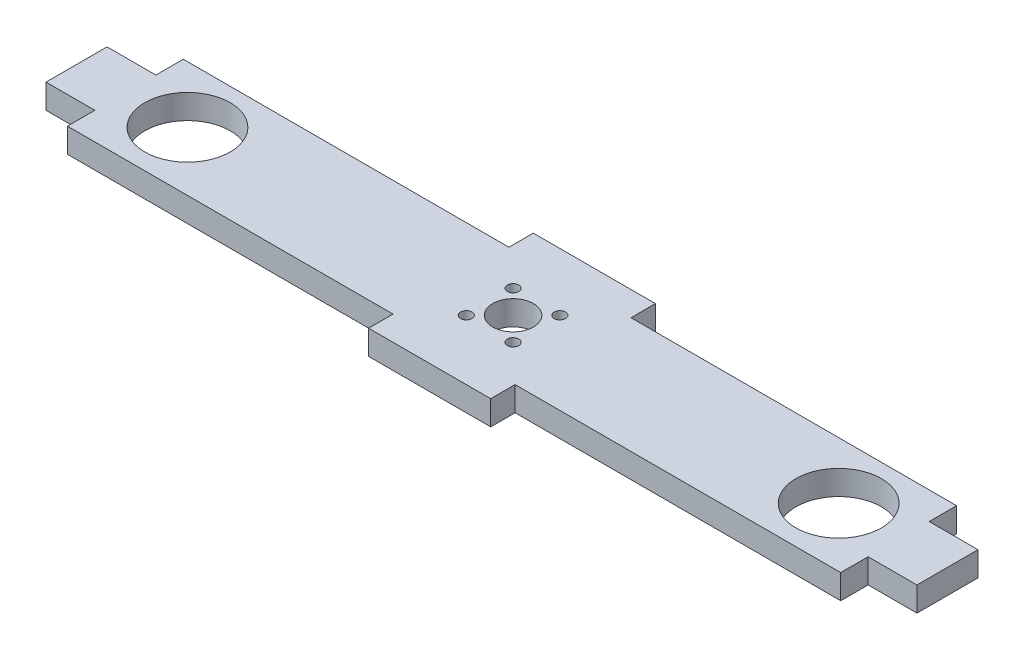
SolidWorks part; units mm, degrees
ref_plane "Front" through (0, 0, 0) normal (0, 0, 1) x (1, 0, 0)
ref_plane "Top" through (0, 0, 0) normal (0, 1, 0) x (1, 0, 0)
ref_plane "Right" through (0, 0, 0) normal (1, 0, 0) x (0, 0, -1)
sketch "Эскиз1" plane through (0, 0, 0) normal (0, 1, 0) x (1, 0, 0)
  line L0 (110.5788, 0.265) -> (-105.6913, 0.265) construction
  line L1 (-95, 14.235) -> (-15, 14.235)
  line L2 (-95, 14.235) -> (-95, 7.5)
  line L3 (-95, -14.235) -> (-15, -14.235)
  line L4 (95, 14.235) -> (95, 7.5)
  line L5 (-95, 14.235) -> (95, -14.235) construction
  line L6 (-95, -14.235) -> (95, 14.235) construction
  line L7 (-80, 48.7611) -> (-80, -31.1923) construction
  line L8 (80, 43.1247) -> (80, -42.2563) construction
  line L9 (0, 43.1247) -> (0, -49.9803) construction
  line L10 (-98.4497, 20.235) -> (101.9556, 20.235) construction
  line L11 (-98.4497, -20.235) -> (110.5788, -20.235) construction
  line L12 (15, 14.235) -> (95, 14.235)
  line L13 (-15, 20.235) -> (15, 20.235)
  line L14 (-15, 20.235) -> (-15, 14.235)
  line L16 (15, 20.235) -> (15, 14.235)
  line L17 (15, -14.235) -> (95, -14.235)
  line L19 (-15, -14.235) -> (-15, -20.235)
  line L20 (-15, -20.235) -> (15, -20.235)
  line L21 (15, -14.235) -> (15, -20.235)
  line L22 (0, 0) -> (111.9405, 0) construction
  line L23 (95, 7.5) -> (107, 7.5)
  line L27 (107, 7.5) -> (107, -7.5)
  line L28 (95, -7.5) -> (95, -14.235)
  line L29 (-95, -7.5) -> (-107, -7.5)
  line L30 (-107, 7.5) -> (-107, -7.5)
  line L31 (95, -7.5) -> (107, -7.5)
  line L32 (-95, 7.5) -> (-107, 7.5)
  line L33 (-95, -7.5) -> (-95, -14.235)
  line L39 (-5.75, -5.485) -> (5.75, 6.015) construction
  line L40 (-5.75, 6.015) -> (5.75, -5.485) construction
  circle A1 centre (-80, 0.265) radius 10.5
  circle A2 centre (80, 0.265) radius 10.5
  circle A3 centre (0, 0.265) radius 5
  circle A4 centre (-5.75, 6.015) radius 1.4
  circle A5 centre (5.75, 6.015) radius 1.4
  circle A6 centre (5.75, -5.485) radius 1.4
  circle A7 centre (-5.75, -5.485) radius 1.4
  point P0 (0, 0)
  point P24 (0, 14.235)
  point P25 (0, -14.235)
  point P36 (95, 0)
  dimension "D4" = 10
  dimension "D7" = 21
  dimension "D18" = 2.8
  dimension "D1" = 190
  dimension "D2" = 28.47
  dimension "D3" = 13.97
  dimension "D5" = 15
  dimension "D6" = 15
  dimension "D8" = 6
  dimension "D9" = 6
  dimension "D10" = 30
  dimension "D11" = 30
  dimension "D12" = 15
  dimension "D13" = 15
  dimension "D14" = 15
  dimension "D15" = 12
  dimension "D16" = 7.5
  dimension "D17" = 11.5
extrude "Бобышка-Вытянуть1" add sketch "Эскиз1" along normal blind 6
